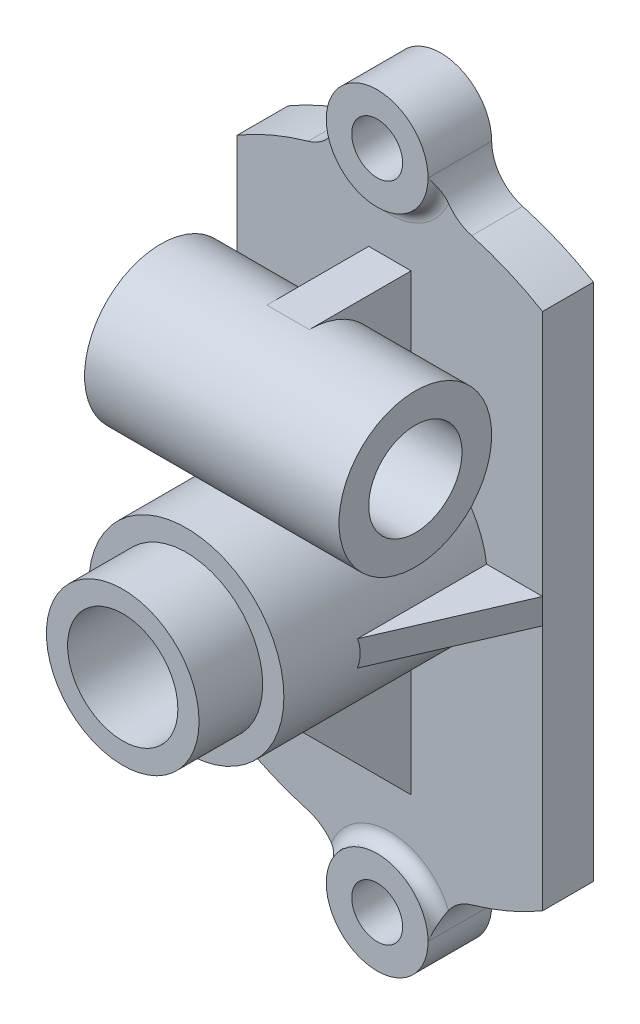
SolidWorks part; units mm, degrees
ref_plane "Front Plane" through (0, 0, 0) normal (1, 0, 0) x (0, 1, 0)
ref_plane "Top Plane" through (0, 0, 0) normal (0, 0, 1) x (0, 1, 0)
ref_plane "Right Plane" through (0, 0, 0) normal (0, 1, 0) x (-1, 0, 0)
sketch "Sketch1" plane through (0, 0, 0) normal (0, 0, 1) x (0, 1, 0)
  line L0 (0, 0) -> (30172.051, 0) construction
  line L1 (0, 0) -> (0, 30172.051) construction
  line L2 (-61.1964, 36) -> (61.1964, 36)
  line L3 (-61.1964, -36) -> (61.1964, -36)
  circle A0 centre (0, 0) radius 13
  circle A1 centre (0, 0) radius 18
  circle A2 centre (0, 0) radius 23
  circle A3 centre (-78, 0) radius 6
  circle A4 centre (-78, 0) radius 12
  circle A5 centre (78, 0) radius 6
  circle A6 centre (78, 0) radius 12
  arc A7 (-61.1964, 36) -> (-68.331, 19.2839) centre (0, 0) ccw
  arc A8 (-68.331, -19.2839) -> (-61.1964, -36) centre (0, 0) ccw
  arc A9 (68.331, 19.2839) -> (61.1964, 36) centre (0, 0) ccw
  arc A10 (-77.9755, 12) -> (-68.331, 19.2839) centre (-77.9551, 22) ccw
  arc A11 (77.9755, 12) -> (68.331, 19.2839) centre (77.9551, 22) cw
  arc A12 (-77.9755, -12) -> (-68.331, -19.2839) centre (-77.9551, -22) cw
  arc A13 (77.9755, -12) -> (68.331, -19.2839) centre (77.9551, -22) ccw
  arc A14 (61.1964, -36) -> (68.331, -19.2839) centre (0, 0) ccw
  dimension "D1" = 26
  dimension "D2" = 36
  dimension "D3" = 46
  dimension "D4" = 12
  dimension "D5" = 24
  dimension "D7" = 72
  dimension "D8" = 71
  dimension "D9" = 10
  dimension "D6" = 156
extrude "Boss-Extrude1" add sketch "Sketch1" along normal blind 12 contours L3 A14 A13 A6 A11 A9 L2 A7 A10 A4 A12 A8 A2 region at (-34.2823, 0, 0)
extrude "Boss-Extrude2" add sketch "Sketch1<3>" along normal blind 15 contours A4 A3 | A6 A5 region at (-8.2369, -69.7463, 0) region at (-8.2537, 86.2369, 0)
sketch "Sketch1<3>" plane through (0, 0, 0) normal (0, 0, 1) x (0, 1, 0) same geometry as "Sketch1"
extrude "Boss-Extrude3" add sketch "Sketch1<4>" along normal blind 60 contours A2 A1 region at (0, -22.3495, 0)
sketch "Sketch1<4>" plane through (0, 0, 0) normal (0, 0, 1) x (0, 1, 0) same geometry as "Sketch1"
extrude "Boss-Extrude4" add sketch "Sketch1<5>" along normal blind 75 contours A1 A0 region at (0, -17.4909, 0)
sketch "Sketch1<5>" plane through (0, 0, 0) normal (0, 0, 1) x (0, 1, 0) same geometry as "Sketch1"
sketch "Sketch2" plane through (0, 0, 0) normal (1, 0, 0) x (0, 1, 0)
  line L1 (-23, 60) -> (-23, 12) construction
  line L2 (-23, 42) -> (-53, 12)
  line L3 (-61.1964, 12) -> (61.1964, 12) construction
  dimension "D1" = 30
  dimension "D2" = 30
rib "Rib1" sketch "Sketch2" sketch "Sketch2" thickness 10 extrusion direction parallel to sketch draft on no parameters "D1"=10
sketch "Sketch3" plane through (0, 0, 0) normal (0, 1, 0) x (-1, 0, 0)
  line L0 (-36, 12) -> (-23, 42)
  line L1 (-23, 60) -> (-23, 12) construction
  dimension "D1" = 30
rib "Rib2" sketch "Sketch3" sketch "Sketch3" thickness 6 extrusion direction parallel to sketch draft on no parameters "D1"=6
mirror "Mirror1" about plane through (0, 0, 0) normal (1, 0, 0) of "Rib2"
sketch "Sketch4" plane through (0, 0, 0) normal (1, 0, 0) x (0, 1, 0)
  line L0 (0, 0) -> (0, 97.1273) construction
  line L1 (-61.1964, 0) -> (61.1964, 0) construction
  line L2 (0, 0) -> (124.4116, 0) construction
  circle A0 centre (36, 36) radius 11
  circle A1 centre (36, 36) radius 18
  point P7 (0, 0)
  dimension "D1" = 36
  dimension "D2" = 22
  dimension "D3" = 36
  dimension "D4" = 36
extrude "Boss-Extrude5" add sketch "Sketch4" along normal mid plane 60
fillet "Fillet1" radius 3 2 edges at (0, 66, 12) (0, -66, 12)
sketch "Sketch5" plane through (0, 0, 0) normal (1, 0, 0) x (0, 1, 0)
  line L0 (54, 36) -> (54, 12)
  line L1 (3, 12) -> (61.1964, 12) construction
  circle A0 centre (36, 36) radius 18 construction
rib "Rib3" sketch "Sketch5" sketch "Sketch5" thickness 10 extrusion direction parallel to sketch draft on no parameters "D1"=10
